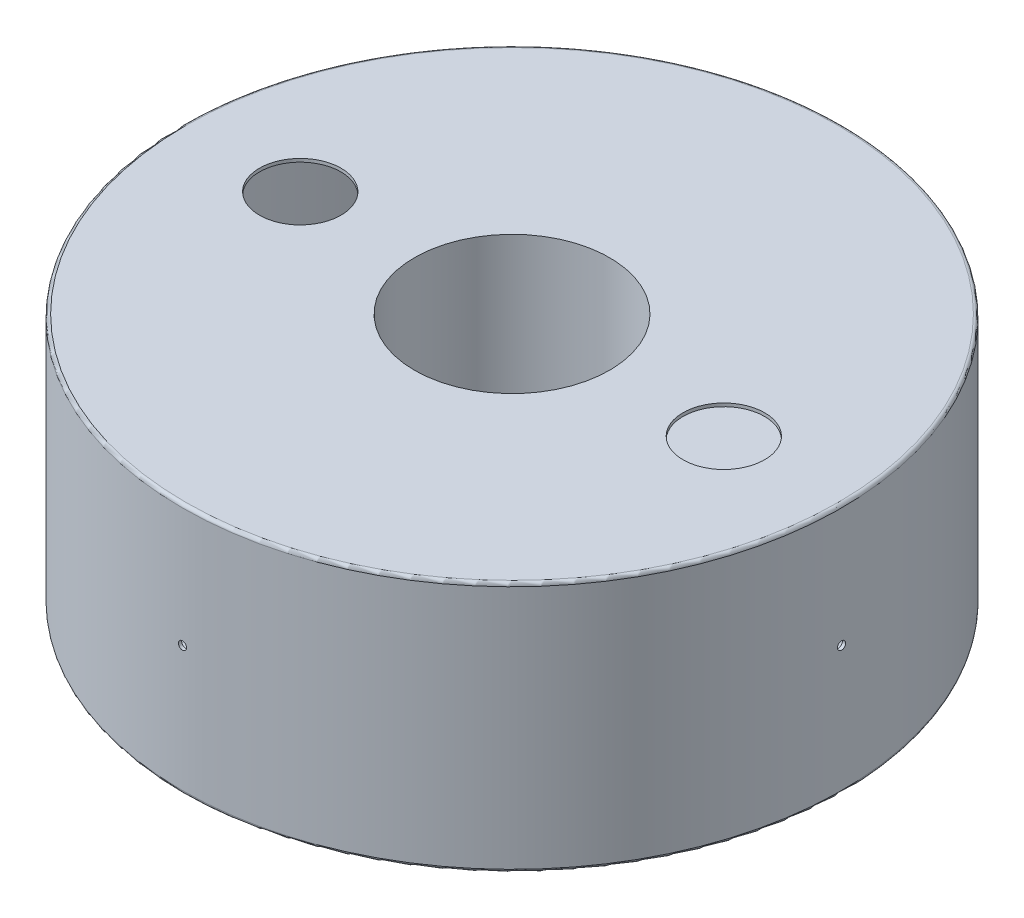
SolidWorks part; units mm, degrees
material "2014 Alloy"
ref_plane "Front Plane" through (0, 0, 0) normal (0, 0, 1) x (1, 0, 0)
ref_plane "Top Plane" through (0, 0, 0) normal (0, 1, 0) x (1, 0, 0)
ref_plane "Right Plane" through (0, 0, 0) normal (1, 0, 0) x (0, 0, -1)
sketch "Sketch9" plane through (0, 0, 0) normal (0, 1, 0) x (1, 0, 0)
  circle A0 centre (0, 0) radius 2000
extrude "Boss-Extrude5" add sketch "Sketch9" along normal blind 1500
sketch "Sketch10" plane through (0, 1500, 0) normal (0, 1, 0) x (1, 0, 0)
  circle A0 centre (0, 0) radius 598.217
extrude "Cut-Extrude3" cut sketch "Sketch10" against normal blind 1500
shell "Shell6" thickness 20 removed face at (0, 0, 598.217) outward yes
sketch "Sketch11" plane through (0, 1520, 0) normal (0, 1, 0) x (1, 0, 0)
  circle A0 centre (0, 0) radius 598.217
extrude "Boss-Extrude6" add sketch "Sketch11" against normal through all
sketch "Sketch13" plane through (0, 1520, 0) normal (0, 1, 0) x (1, 0, 0)
  circle A0 centre (0, 0) radius 618.217
extrude "Boss-Extrude7" add sketch "Sketch13" against normal through all
sketch "Sketch14" plane through (0, 1520, 0) normal (0, 1, 0) x (1, 0, 0)
  circle A0 centre (0, 0) radius 598.217
extrude "Cut-Extrude5" cut sketch "Sketch14" against normal through all
fillet "Fillet2" radius 20 2 edges at (0, 1520, 2020) (0, -20, 2020)
sketch "Sketch16" plane through (0, 1520, 0) normal (0, 1, 0) x (1, 0, 0)
  circle A0 centre (-1298.217, 0) radius 250
  circle A1 centre (1298.217, 0) radius 250
  dimension "D1" = 2
extrude "Cut-Extrude6" cut sketch "Sketch16" against normal blind 547 and the other way through all
sketch "Sketch19" plane through (0, 0, 0) normal (0, 0, 1) x (1, 0, 0)
  circle A0 centre (0, 770) radius 24.963
extrude "Cut-Extrude11" cut sketch "Sketch19" along normal blind 300 and the other way blind 100 from offset 1800
pattern_circular "CirPattern1" count 4 every 90 about axis through (0, 1520, 0) along (0, 1, 0) of "Cut-Extrude11"
